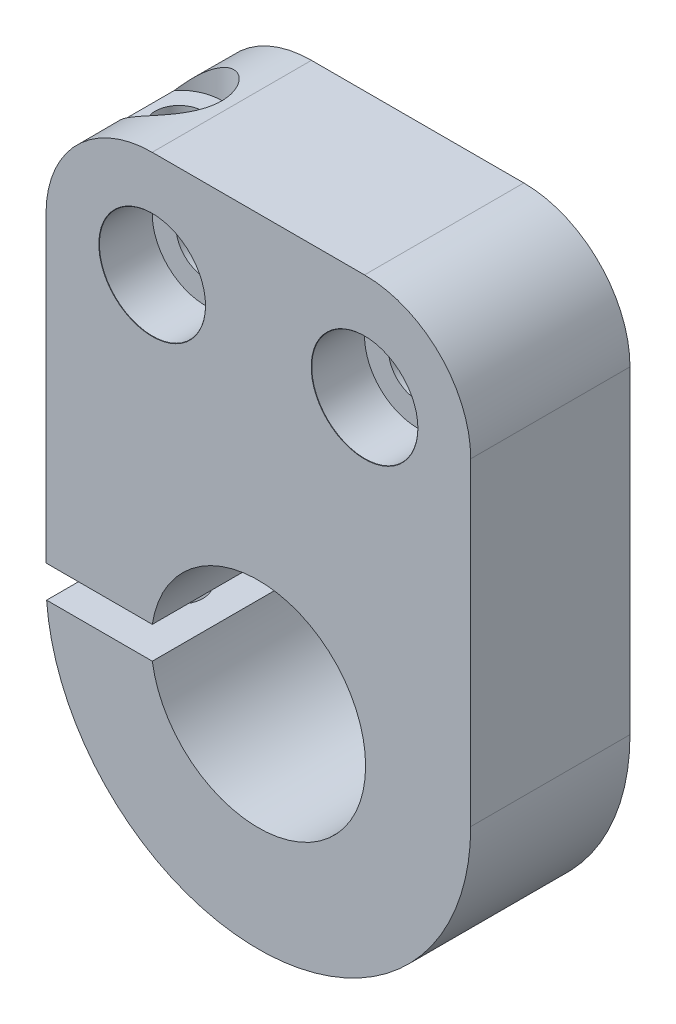
SolidWorks part; units mm, degrees
ref_plane "Front Plane" through (0, 0, 0) normal (0, 0, 1) x (1, 0, 0)
ref_plane "Top Plane" through (0, 0, 0) normal (0, 1, 0) x (1, 0, 0)
ref_plane "Right Plane" through (0, 0, 0) normal (1, 0, 0) x (0, 0, -1)
sketch "Sketch2" plane through (0, 0, 0) normal (0, 0, 1) x (1, 0, 0)
  line L0 (-20, 0) -> (-20, 40)
  line L1 (-20, 40) -> (20, 40)
  line L2 (20, 40) -> (20, 0)
  line L3 (20, 0) -> (-20, 0)
  circle A0 centre (0, 0) radius 20
  circle A1 centre (0, 0) radius 10.1
  dimension "D1" = 20.2
  dimension "D2" = 40
  dimension "D3" = 40
extrude "Boss-Extrude1" add sketch "Sketch2" along normal blind 15 contours A0 L2 L1 L0 | A1 L3 A0 | A1 L3 A0 region at (0, 19.5528, 0) region at (0, 27.4438, 0) region at (-15.05, -0.4472, 0)
sketch "Sketch3" plane through (0, 0, 15) normal (0, 0, 1) x (1, 0, 0)
  line L0 (-20, 0) -> (-20, 40) construction
  line L1 (-20, 1.5) -> (-9.988, 1.5)
  line L2 (-20, 1.5) -> (-20, -1.5)
  line L3 (-20, -1.5) -> (-9.988, -1.5)
  line L4 (-9.988, 1.5) -> (-9.988, -1.5)
  circle A2 centre (0, 0) radius 10.1 construction
  point P4 (-9.988, 0)
  dimension "D1" = 3
extrude "Cut-Extrude1" cut sketch "Sketch3" against normal through all
sketch "Sketch11" plane through (0, 40, 0) normal (0, 1, 0) x (1, 0, 0)
  line L1 (-19.9437, -15) -> (-9.988, -15) construction
  line L2 (-20, -15) -> (-20, 0) construction
  point P0 (-14.9658, -7.5)
  point P10 (-14.9658, -15)
  point P13 (-20, -7.5)
hole_wizard "CBORE for M4 SHCS1" positions "Sketch11" profile "Sketch10" counterbore size "M4" standard "ANSI Metric" end condition through all
sketch "Sketch10" plane through (-14.9658, 40, 7.5) normal (1, 0, 0) x (0, 0, 1)
  line L0 (0, 0) -> (0, 60)
  line L1 (0, 60) -> (2.25, 60)
  line L3 (2.25, 60) -> (2.25, 4)
  line L4 (4, 4) -> (2.25, 4)
  line L5 (4, 4) -> (4, 0.025)
  line L6 (4, 0.025) -> (4.025, 0)
  line L7 (4.025, 0) -> (0, 0)
  line L8 (-4, 0.025) -> (-4.025, 0) construction
  line L11 (0, -6.35) -> (0, 107.95) construction
  dimension "Thru Hole Dia." = 4.5
  dimension "Thru Hole Depth" = 60
  dimension "C'Bore Dia." = 8
  dimension "C'Bore Depth" = 4
  dimension "Near C'Sink Dia." = 8.05
  dimension "Near C'Sink Angle" = 90
sketch "Sketch17" plane through (0, 0, 15) normal (0, 0, 1) x (1, 0, 0)
  line L0 (-10, 30) -> (10, 30) construction
  line L2 (-20, 40) -> (20, 40) construction
  point P0 (-10, 30)
  point P2 (10, 30)
  point P9 (0, 30)
  dimension "D1" = 20
  dimension "D2" = 10
hole_wizard "CBORE for M5 SHCS1" positions "Sketch17" profile "Sketch15" counterbore size "M5" standard "ANSI Metric" end condition through all
sketch "Sketch15" plane through (-10, 30, 15) normal (1, 0, 0) x (0, -1, 0)
  line L0 (0, 0) -> (0, 15)
  line L1 (0, 15) -> (2.75, 15)
  line L3 (2.75, 15) -> (2.75, 5)
  line L4 (5, 5) -> (2.75, 5)
  line L5 (5, 5) -> (5, 0.025)
  line L6 (5, 0.025) -> (5.025, 0)
  line L7 (5.025, 0) -> (0, 0)
  line L8 (-5, 0.025) -> (-5.025, 0) construction
  line L11 (0, -6.35) -> (0, 107.95) construction
  dimension "Thru Hole Dia." = 5.5
  dimension "Thru Hole Depth" = 15
  dimension "C'Bore Dia." = 10
  dimension "C'Bore Depth" = 5
  dimension "Near C'Sink Dia." = 10.05
  dimension "Near C'Sink Angle" = 90
fillet "Fillet1" radius 10 2 edges at (-20, 40, 7.5) (20, 40, 7.5)
ref_plane "Plane1" through (0, -9, 0) normal (0, 1, 0) x (1, 0, 0)
sketch "Sketch18" plane through (0, -9, 0) normal (0, 1, 0) x (1, 0, 0)
  line L0 (-17.0443, -3.9) -> (-12.8874, -3.9)
  line L1 (-12.8874, -3.9) -> (-10.8089, -7.5)
  line L2 (-10.8089, -7.5) -> (-12.8874, -11.1)
  line L3 (-12.8874, -11.1) -> (-17.0443, -11.1)
  line L4 (-17.0443, -11.1) -> (-19.1228, -7.5)
  line L5 (-19.1228, -7.5) -> (-17.0443, -3.9)
  line L6 (-18.0835, -9.3) -> (-11.8481, -5.7) construction
  line L8 (-20, -15) -> (-20, 0) construction
  line L10 (-19.9437, -15) -> (-9.988, -15) construction
  point P8 (-11.8481, -5.7)
  point P12 (-20, -7.5)
  point P13 (-14.9658, -7.5)
  point P19 (-14.9658, -15)
  dimension "D1" = 120
  dimension "D2" = 120
  dimension "D3" = 7.2
extrude "Cut-Extrude2" cut sketch "Sketch18" against normal through all
